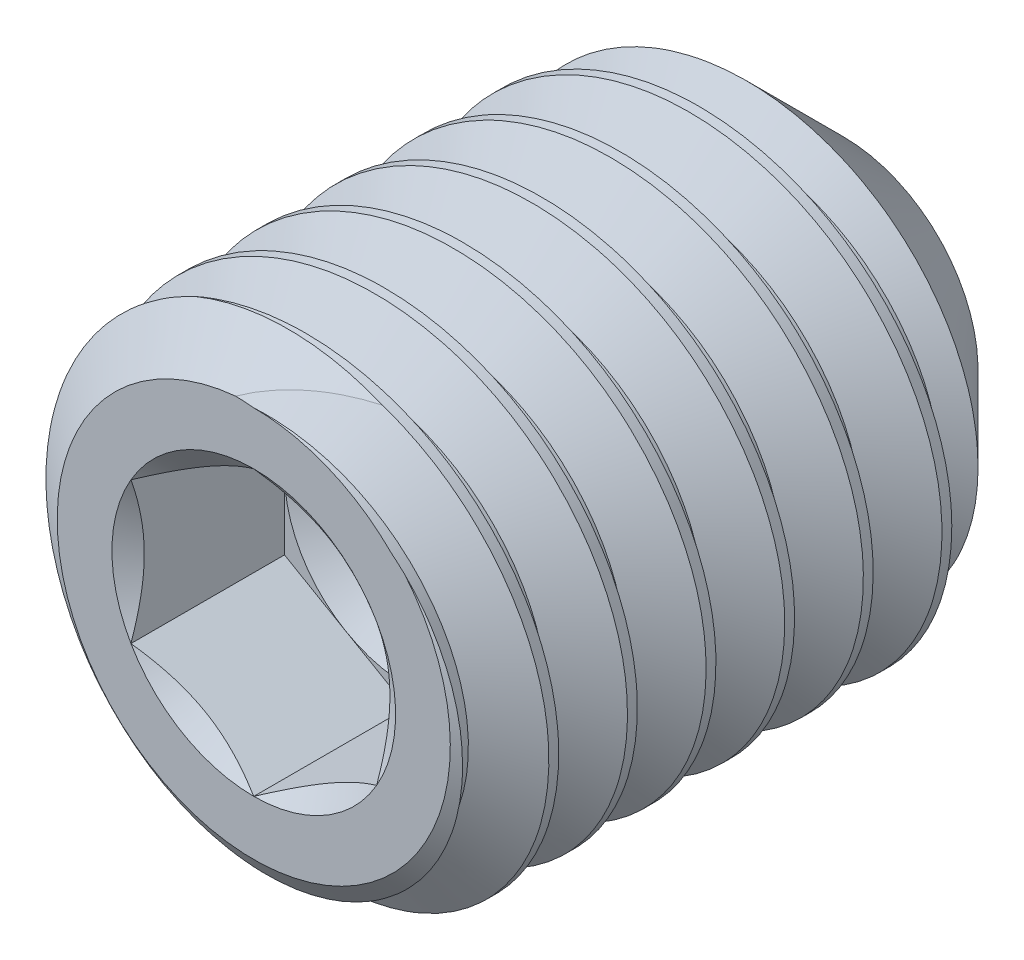
SolidWorks part; units mm, degrees
ref_plane "Front" through (0, 0, 0) normal (0, 0, 1) x (1, 0, 0)
ref_plane "Top" through (0, 0, 0) normal (0, 1, 0) x (1, 0, 0)
ref_plane "Right" through (0, 0, 0) normal (1, 0, 0) x (0, 0, -1)
sketch "Body Sketch" plane through (0, 0, 0) normal (1, 0, 0) x (0, 0, -1)
  line L0 (-2.5884, 0) -> (-2.5884, 2)
  line L1 (-2.5884, 2) -> (-2.2383, 2.5)
  line L2 (-2.2383, 2.5) -> (2.2815, 2.5)
  line L3 (2.2815, 2.5) -> (3.4116, 1.3699)
  line L4 (0.0216, 2.5) -> (0.0216, -2.5) construction
  line L5 (2.5884, 0) -> (-2.5884, 0)
  line L6 (-2.5884, 2) -> (-2.5884, -2) construction
  line L7 (2.5884, 0) -> (3.4116, 1.3699)
  line L8 (2.5884, 0) -> (3.4116, -1.3699) construction
  line L10 (2.5884, 0) -> (3.4116, 0) construction
  line L11 (3.4116, 1.3699) -> (3.4116, 0) construction
  point P11 (0.0216, 0)
  dimension "Length" = 6
  dimension "Top Chamfer" = 35
  dimension "Diameter" = 5
  dimension "D1" = 4
  dimension "D2" = 118
  dimension "D3" = 45
revolve "Body Revolve" add sketch "Body Sketch" angle 360 about L5
ref_plane "Bottom of Tip Plane" through (0, 0, -3.4116) normal (0, 0, 1) x (1, 0, 0)
sketch "Test Sketch" plane through (0, 0, 0) normal (1, 0, 0) x (0, 0, -1)
  line L0 (0, 0) -> (8.9071, 0)
sketch "Spiral Sketch" plane through (0, 0, -3.4116) normal (0, 0, 1) x (1, 0, 0)
  circle A0 centre (0, 0) radius 2.5 construction
  circle A1 centre (0, 0) radius 2.5
curve "Helix/Spiral" pitch 0.8 height 6.8 radius 2.5 centre (0, 0, -3.4116) axis (0, 0, 1) start towards (0, 1, 0) parameters "Thread Pitch"=0.8
sketch "Cut Sweep Sketch" plane through (0, 0, 0) normal (1, 0, 0) x (0, 0, -1)
  line L0 (3.4116, 2.5) -> (4.1116, 2.5)
  line L1 (4.1116, 2.5) -> (3.8116, 1.9804)
  line L2 (3.8116, 1.9804) -> (3.7116, 1.9804)
  line L3 (3.7116, 1.9804) -> (3.4116, 2.5)
  line L4 (3.5616, 2.2402) -> (3.9616, 2.2402) construction
  line L6 (-2.2383, 2.5) -> (2.2815, 2.5) construction
  dimension "D1" = 0.1
  dimension "D3" = 60
  dimension "D2" = 0.4
sweep "Cut Sweep" cut profiles "Cut Sweep Sketch" path "Helix/Spiral" align with end faces yes
sketch "Hex Sketch" plane through (0, 0, 2.5884) normal (0, 0, 1) x (1, 0, 0)
  line L1 (0, 1.4434) -> (-1.25, 0.7217)
  line L2 (-1.25, 0.7217) -> (-1.25, -0.7217)
  line L3 (-1.25, -0.7217) -> (0, -1.4434)
  line L4 (0, -1.4434) -> (1.25, -0.7217)
  line L5 (1.25, -0.7217) -> (1.25, 0.7217)
  line L6 (1.25, 0.7217) -> (0, 1.4434)
  circle A0 centre (0, 0) radius 1.25 construction
  dimension "Hex" = 2.5
extrude "Hex Extrude" cut sketch "Hex Sketch" against normal blind 1.5625
sketch "Hex Entry Sketch" plane through (0, 0, 2.5884) normal (0, 0, 1) x (1, 0, 0)
  circle A0 centre (0, 0) radius 1.4434
extrude "Hex Entry Extrude" cut sketch "Hex Entry Sketch" against normal through all draft 55
sketch "Hex Bottom Sketch" plane through (0, 0, 1.0259) normal (0, 0, 1) x (1, 0, 0)
  circle A0 centre (0, 0) radius 1.25 construction
  circle A1 centre (0, 0) radius 1.25
extrude "Hex Bottom Extrude" cut sketch "Hex Bottom Sketch" against normal through all draft 60
equation "\"D1@Cut Sweep Sketch\" = \"Thread Pitch@Helix/Spiral\" * .125"
equation "\"D2@Cut Sweep Sketch\" = \"Thread Pitch@Helix/Spiral\" * .5"
equation "\"D3@Helix/Spiral\" = \"Length@Body Sketch\" + \"Thread Pitch@Helix/Spiral\""
equation "\"hex Depth@Hex Extrude\" = \"Hex@Hex Sketch\" * .625"
equation "\"D1@Body Sketch\" = \"Diameter@Body Sketch\" * .8"
equation "\"Diameter\"= 5mm"
equation "\"Thread Pitch\"= 0.8mm"
equation "\"Hex Size\"= 2.5mm"
equation "\"Diameter@Body Sketch\"=\"Diameter\""
equation "\"Thread Pitch@Helix/Spiral\"=\"Thread Pitch\""
equation "\"Hex@Hex Sketch\"=\"Hex Size\""
